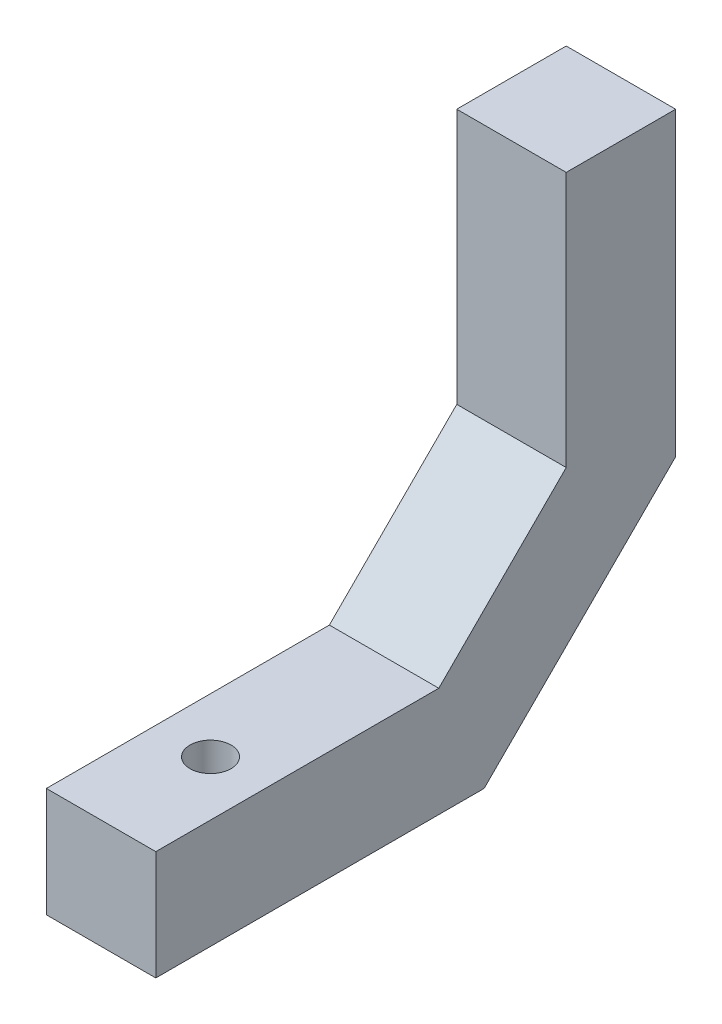
SolidWorks part; units mm, degrees
ref_plane "Front Plane" through (0, 0, 0) normal (0, 0, 1) x (1, 0, 0)
ref_plane "Top Plane" through (0, 0, 0) normal (0, 1, 0) x (1, 0, 0)
ref_plane "Right Plane" through (0, 0, 0) normal (1, 0, 0) x (0, 0, -1)
ref_axis "Z" through (0, 0, 39.9) along (0, 0, -1)
sketch "Sketch1" plane through (0, 0, 0) normal (1, 0, 0) x (0, 0, -1)
  line L0 (-8, 4) -> (0, 4)
  line L1 (0, 4) -> (0, -18)
  line L2 (0, -18) -> (-14, -32)
  line L3 (-14, -32) -> (-30, -32)
  line L4 (-30, -32) -> (-30, -24) construction
  line L5 (-30, -24) -> (-17.3137, -24)
  line L6 (-17.3137, -24) -> (-8, -14.6863)
  line L7 (-8, -14.6863) -> (-8, 4)
  line L8 (-13.4134, -20.0997) -> (-7.7566, -25.7566) construction
  line L10 (-30, -24) -> (-38, -24)
  line L11 (-30, -24) -> (-30, -32) construction
  line L12 (-30, -32) -> (-38, -32)
  line L13 (-38, -24) -> (-38, -32)
  dimension "D1" = 8
  dimension "D2" = 30
  dimension "D3" = 32
  dimension "D4" = 4
  dimension "D5" = 135
  dimension "D6" = 14
  dimension "D7" = 8
extrude "Boss-Extrude1" add sketch "Sketch1" along normal blind 4 and the other way blind 4
sketch "Sketch3" plane through (0, -24, 0) normal (0, 1, 0) x (1, 0, 0)
  line L0 (-4.4, 0) -> (4.4, 0) construction
  line L1 (0, -18.7) -> (0, 18.7) construction
  circle A0 centre (0, -30) radius 1.5
  dimension "D2" = 3
  dimension "D1" = 30
extrude "Cut-Extrude1" cut sketch "Sketch3" against normal through all
ref_axis "Axis1" through (0, -24, 30) along (0, 1, 0)
equation "\"rbracket-width\"= 8"
equation "\"D1@Boss-Extrude1\"=\"rbracket-width\"/2"
equation "\"D2@Boss-Extrude1\"=\"rbracket-width\"/2"
equation "\"EyeCaptureRadius\"= ( \"EyeDiameter\" + \"EyeClearance\" ) / 2"
equation "\"rbracket_planetocenterline_dist\"= \"BasePlaneDistance\""
equation "\"D2@Sketch1\"=\"rbracket_planetocenterline_dist\""
equation "\"EyeDiameter\" = 28"
equation "\"BasePlaneDistance\" = 30"
equation "\"EyeClearance\" = 2"
equation "\"D1@Sketch1\"=\"rbracket-width\""
equation "\"D3@Sketch1\"=(\"EyeDiameter\"+\"EyeClearance\"+\"EyeClearance\")/2 + \"L2Thickness\" + \"rbracket-width\""
equation "\"D4@Sketch1\"=\"rbracket-width\"/2"
equation "\"D6@Sketch1\"=\"EyeDiameter\"/2"
equation "\"D7@Sketch1\"=\"rbracket-width\""
equation "\"D1@Sketch3\"=\"BasePlaneDistance\""
equation "\"L2Thickness\" = 8"
